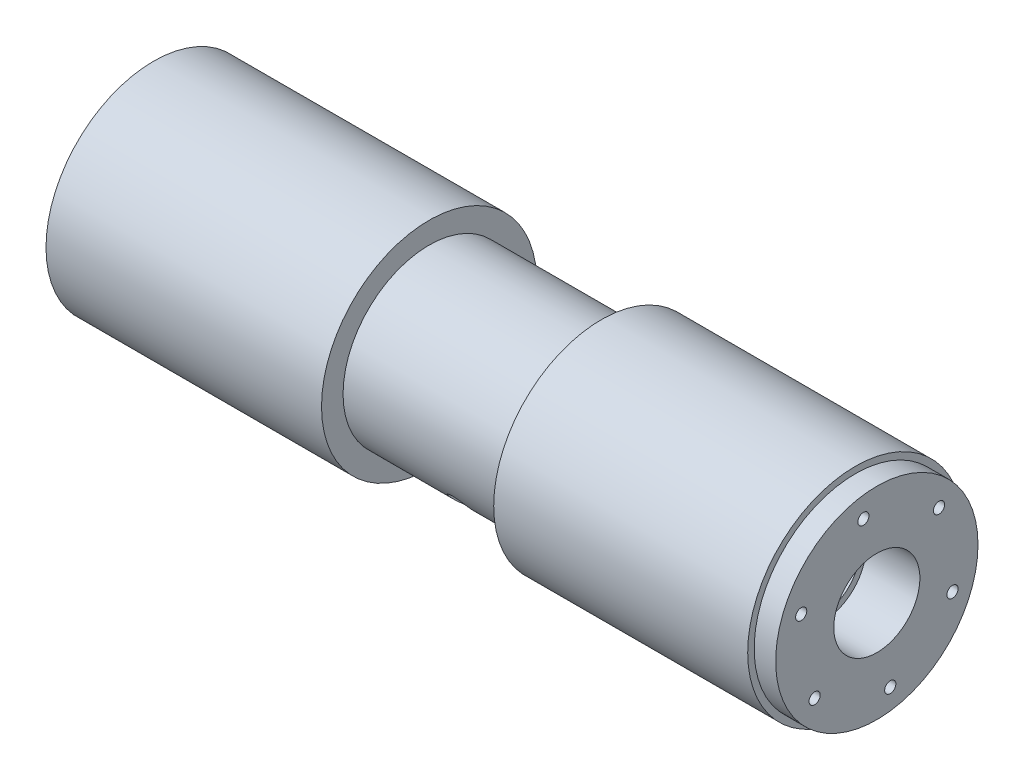
SolidWorks part; units mm, degrees
material "Nylon 101"
ref_plane "Front Plane" through (0, 0, 0) normal (0, 0, 1) x (1, 0, 0)
ref_plane "Top Plane" through (0, 0, 0) normal (0, 1, 0) x (1, 0, 0)
ref_plane "Right Plane" through (0, 0, 0) normal (1, 0, 0) x (0, 0, -1)
sketch "Sketch1" plane through (0, 0, 0) normal (1, 0, 0) x (0, 0, -1)
  circle A0 centre (0, 0) radius 31.75
  circle A1 centre (0, 0) radius 10.795
  dimension "D2" = 63.5
  dimension "D1" = 20.955
extrude "Boss-Extrude1" add sketch "Sketch1" along normal blind 106.68
sketch "Sketch2" plane through (0, 0, 0) normal (-1, 0, 0) x (0, 0, 1)
  circle A0 centre (0, 0) radius 12.7
extrude "Cut-Extrude1" cut sketch "Sketch2" against normal blind 15.875
mirror "Mirror1" about plane through (106.68, 0, 0) normal (1, 0, 0) of "Cut-Extrude1", "Boss-Extrude1"
sketch "Sketch3" plane through (0, 0, 0) normal (-1, 0, 0) x (0, 0, 1)
  circle A0 centre (0, 0) radius 25.4
  dimension "D1" = 50.8
extrude "Cut-Extrude2" cut sketch "Sketch3" against normal blind 50.8 from offset 81.28 flip side to cut offset against normal yes
sketch "Sketch5" plane through (0, 0, 0) normal (0, 0, 1) x (1, 0, 0)
  line L0 (213.36, -31.75) -> (213.36, 31.75) construction
  line L1 (132.08, 25.4) -> (81.28, 25.4) construction
  circle A0 centre (109.22, -17.4625) radius 3.175
  dimension "D1" = 6.35
  dimension "D3" = 42.8625
  dimension "D2" = 104.14
extrude "Cut-Extrude3" cut sketch "Sketch5" against normal blind 25.4 and the other way blind 25.4
hole_wizard "M4x0.7 Tapped Hole1" positions "Sketch10" profile "Sketch9" tap size "M4x0.7" standard "ANSI Metric"
sketch "Sketch10" plane through (213.36, 0, 0) normal (1, 0, 0) x (0, 0, -1)
  line L1 (22.3163, -8.3078) -> (18.3529, 15.1725)
  line L2 (18.3529, 15.1725) -> (-3.9634, 23.4804)
  line L3 (-3.9634, 23.4804) -> (-22.3163, 8.3078)
  line L4 (-22.3163, 8.3078) -> (-18.3529, -15.1725)
  line L5 (-18.3529, -15.1725) -> (3.9634, -23.4804)
  line L6 (3.9634, -23.4804) -> (22.3163, -8.3078)
  circle A0 centre (0, 0) radius 23.8125
  circle A1 centre (0, 0) radius 20.6222 construction
  point P0 (22.3163, -8.3078)
  point P2 (3.9634, -23.4804)
  point P4 (18.3529, 15.1725)
  point P6 (-3.9634, 23.4804)
  point P8 (-22.3163, 8.3078)
  point P10 (-18.3529, -15.1725)
  dimension "D1" = 47.625
sketch "Sketch9" plane through (213.36, -8.3078, -22.3163) normal (0, 1, 0) x (0, 0, -1)
  line L0 (0, 0) -> (0, 10.8974)
  line L1 (0, 10.8974) -> (1.65, 9.906)
  line L2 (1.65, 9.906) -> (1.65, 0)
  line L5 (1.65, 0) -> (0, 0)
  line L10 (0, 10.8974) -> (-1.65, 9.906) construction
  line L11 (0, -6.35) -> (0, 107.95) construction
  dimension "Tap Drill Dia." = 3.3
  dimension "Tap Drill Depth" = 9.906
  dimension "Drill Angle" = 118
sketch "Sketch11" plane through (213.36, 0, 0) normal (1, 0, 0) x (0, 0, -1)
  circle A0 centre (0, 0) radius 29.845
  dimension "D1" = 59.69
extrude "Cut-Extrude4" cut sketch "Sketch11" against normal blind 6.35 flip side to cut
